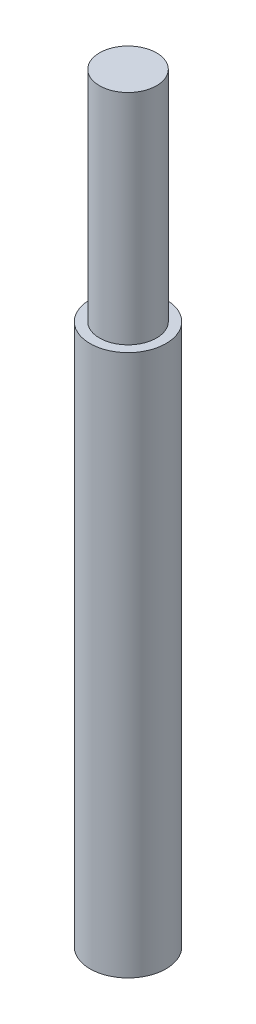
SolidWorks part; units mm, degrees
ref_plane "Front Plane" through (0, 0, 0) normal (0, 0, 1) x (1, 0, 0)
ref_plane "Top Plane" through (0, 0, 0) normal (0, 1, 0) x (1, 0, 0)
ref_plane "Right Plane" through (0, 0, 0) normal (1, 0, 0) x (0, 0, -1)
sketch "Sketch1" plane through (0, 0, 0) normal (0, 1, 0) x (1, 0, 0)
  circle A0 centre (0, 0) radius 4
  dimension "D1" = 8
extrude "Boss-Extrude1" add sketch "Sketch1" along normal blind 57
sketch "Sketch2" plane through (0, 57, 0) normal (0, 1, 0) x (1, 0, 0)
  circle A0 centre (0, 0) radius 3
  dimension "D1" = 6
extrude "Boss-Extrude2" add sketch "Sketch2" along normal blind 23
